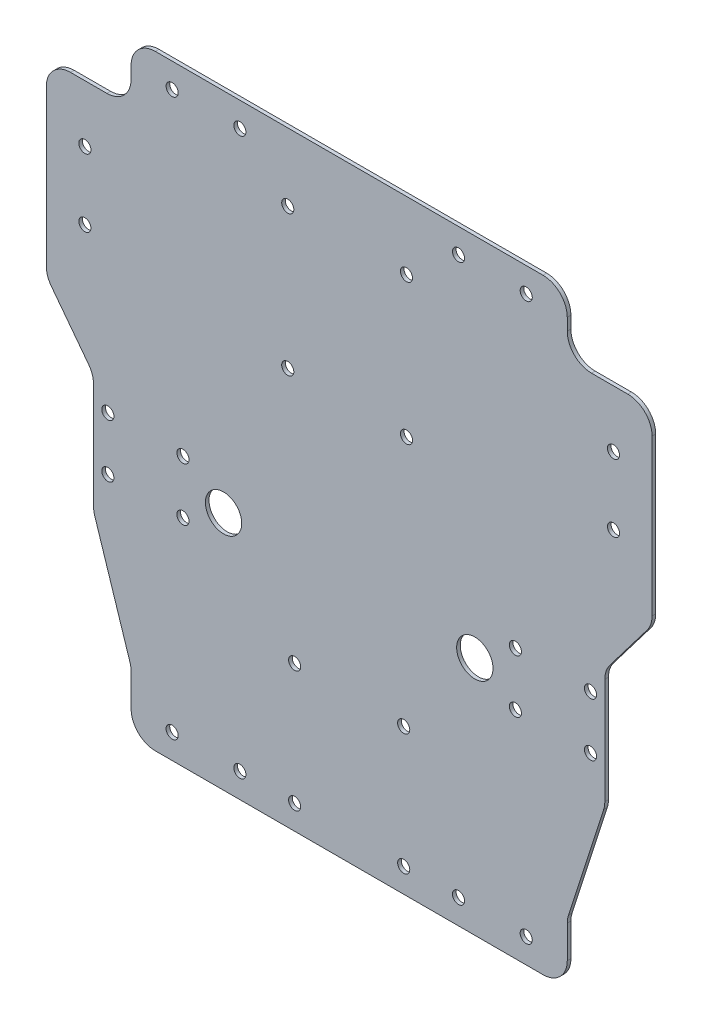
SolidWorks part; units mm, degrees
other "Markup1"
sketch "Sketch7" plane through (25, 0, 0) normal (-0.133, -0.1918, 0.9724) x (0.9904, 0.0125, 0.1379)
material "6061 Alloy"
ref_plane "Front Plane" through (0, 0, 0) normal (0, 0, 1) x (1, 0, 0)
ref_plane "Top Plane" through (0, 0, 0) normal (0, 1, 0) x (1, 0, 0)
ref_plane "Right Plane" through (0, 0, 0) normal (1, 0, 0) x (0, 0, -1)
sketch "Sketch1" plane through (0, 0, 0) normal (0, 0, 1) x (1, 0, 0)
  line L1 (0, 0) -> (300, 0)
  line L2 (0, 0) -> (0, 250)
  line L3 (0, 250) -> (300, 250)
  line L4 (300, 0) -> (300, 250)
  dimension "D1" = 300
  dimension "D2" = 250
extrude "Boss-Extrude1" add sketch "Sketch1" against normal blind 1.5
sketch "Motor Center Line" plane through (0, 0, -1.5) normal (0, 0, -1) x (-1, 0, 0)
  line L0 (0, 100) -> (-300, 100) construction
  line L3 (-300, 250) -> (0, 250) construction
  dimension "D1" = 150
sketch "Sketch2" plane through (0, 0, 0) normal (0, 0, 1) x (1, 0, 0)
  line L0 (150, 0.825) -> (150, -0.825) construction
  line L1 (0, 0) -> (20, 0)
  line L2 (0, 0) -> (0, 20)
  line L3 (0, 20) -> (20, 20)
  line L4 (20, 0) -> (20, 20)
  line L5 (300, 20) -> (280, 20)
  line L6 (280, 0) -> (280, 20)
  line L7 (300, 0) -> (280, 0)
  line L8 (300, 0) -> (300, 20)
  line L10 (0, 125) -> (300, 125) construction
  line L11 (0, 250) -> (0, 0) construction
  line L12 (300, 0) -> (300, 250) construction
  line L13 (300, 250) -> (300, 230)
  line L14 (300, 250) -> (280, 250)
  line L15 (280, 250) -> (280, 230)
  line L16 (300, 230) -> (280, 230)
  line L17 (0, 230) -> (20, 230)
  line L18 (20, 250) -> (20, 230)
  line L19 (0, 250) -> (20, 250)
  line L20 (0, 250) -> (0, 230)
  dimension "D1" = 20
sketch "Sketch3" plane through (0, 0, 0) normal (0, 0, 1) x (1, 0, 0)
  line L0 (150, 250) -> (150, 0) construction
  line L1 (0, 0) -> (25, 0)
  line L2 (0, 0) -> (0, 25)
  line L3 (0, 25) -> (25, 25)
  line L4 (25, 0) -> (25, 25)
  line L5 (300, 250) -> (0, 250) construction
  line L6 (0, 0) -> (300, 0) construction
  line L7 (0, 125) -> (300, 125) construction
  line L8 (0, 250) -> (0, 0) construction
  line L9 (300, 0) -> (300, 250) construction
  line L10 (300, 25) -> (275, 25)
  line L11 (275, 0) -> (275, 25)
  line L12 (300, 0) -> (275, 0)
  line L13 (300, 0) -> (300, 25)
  line L14 (300, 250) -> (300, 225)
  line L15 (300, 250) -> (275, 250)
  line L16 (275, 250) -> (275, 225)
  line L17 (300, 225) -> (275, 225)
  line L18 (0, 225) -> (25, 225)
  line L19 (25, 250) -> (25, 225)
  line L20 (0, 250) -> (25, 250)
  line L21 (0, 250) -> (0, 225)
  line L22 (255.5, 73) -> (275, 47.3437)
  line L23 (255.5, 73) -> (255.5, 121.6874)
  line L24 (255.5, 121.6874) -> (275, 147.3437)
  line L25 (275, 147.3437) -> (300, 147.3437)
  line L26 (300, 147.3437) -> (300, 25)
  line L27 (275, 47.3437) -> (275, 25)
  line L28 (44.5, 73) -> (25, 47.3437)
  line L29 (25, 47.3437) -> (25, 25)
  line L30 (44.5, 73) -> (44.5, 121.6874)
  line L31 (265.5, 121.25) -> (265.5, 78.75) construction
  line L32 (44.5, 121.6874) -> (25, 147.3437)
  line L37 (287.5, 147.3437) -> (287.5, 225)
  line L38 (25, 147.3437) -> (0, 147.3437)
  line L39 (12.5, 147.3437) -> (12.5, 225)
  circle A0 centre (201.85, 99.1258) radius 7.5
  circle A1 centre (98.15, 99.1258) radius 7.5
  ellipse E4 centre (201.85, 99.7743) end of major axis (201.2, 99.7743) minor radius 0.6484 construction
  line M15 (0, 250) -> (0, 0)
  line M16 (0, 0) -> (300, 0)
  line M17 (300, 0) -> (300, 250)
  line M18 (300, 250) -> (0, 250)
  dimension "D3" = 15
  dimension "D1" = 25
  dimension "D2" = 10
  dimension "D4" = 100
extrude "Cut-Extrude1" cut sketch "Sketch3" against normal through all both and the other way through all contours L11 L10 M16 M17 | L25 L24 L23 L10 M17 | L17 L16 M17 M18 | L19 L18 M18 M15 | L3 M15 | L4 L3 M16 M15 | A1 | A0 | L18 M15 | L37 L25 L17 M17 region at (12.5, 12.5, 0) region at (19.2941, 89.7643, 0) region at (287.5, 12.5, 0) region at (6.25, 186.1719, 0) region at (280.7059, 89.7643, 0) region at (12.5, 237.5, 0) region at (293.75, 186.1719, 0) region at (287.5, 237.5, 0) region at (201.85, 99.1258, 0) region at (98.15, 99.1258, 0)
sketch "Sketch4" plane through (0, 0, 0) normal (0, 0, 1) x (1, 0, 0)
  arc A0 (174.9953, 164.0221) -> (172.2953, 164.0221) centre (173.6453, 164.0221) ccw construction
  arc A1 (125.9953, 164.0221) -> (123.2953, 164.0221) centre (124.6453, 164.0221) ccw construction
  arc A4 (125.9953, 222.0221) -> (123.2953, 222.0221) centre (124.6453, 222.0221) ccw construction
  arc A5 (174.9953, 222.0221) -> (172.2953, 222.0221) centre (173.6453, 222.0221) ccw construction
  point P0 (40.9169, 201.47)
  point P1 (40.9169, 173.53)
  point P3 (76.94, 239.84)
  point P4 (104.88, 239.84)
  point P5 (195.12, 239.84)
  point P9 (223.06, 239.84)
  point P11 (259.0831, 201.47)
  point P13 (259.0831, 173.53)
  point P15 (195.12, 10.16)
  point P17 (223.06, 10.16)
  point P19 (76.94, 10.16)
  point P21 (104.88, 10.16)
  point P23 (127.5, 10)
  point P25 (172.5, 10)
  point P27 (127.5, 60)
  point P29 (172.5, 60)
  point P31 (124.6453, 164.0221)
  point P33 (173.6453, 164.0221)
  point P34 (0, 0)
  point P35 (124.6453, 222.0221)
  point P37 (173.6453, 222.0221)
  point P39 (218.6, 111)
  point P41 (249.6, 111)
  point P43 (249.6, 89)
  point P45 (218.6, 89)
  point P47 (81.4, 89.0063)
  point P49 (50.4, 89.0063)
  point P51 (81.4, 111.0063)
  point P53 (50.4, 111.0063)
  point P55 (0, 0)
  point P57 (0, 0)
  point P61 (0, 0)
  point P62 (0, 0)
  point P66 (0, 0)
  point P68 (0, 0)
  point P69 (0, 0)
  point P71 (0, 0)
sketch "Sketch6" plane through (0, 0, 0) normal (0, 0, 1) x (1, 0, 0)
  line L1 (275, 0) -> (240, 0)
  line L2 (275, 0) -> (275, 25)
  line L3 (275, 25) -> (240, 25)
  line L4 (240, 0) -> (240, 25)
  line L5 (240, 25) -> (255.5, 73)
  line L6 (150, 250) -> (150, 0) construction
  line L7 (275, 250) -> (25, 250) construction
  line L8 (25, 0) -> (275, 0) construction
  line L9 (60, 25) -> (44.5, 73)
  line L10 (25, 25) -> (60, 25)
  line L11 (60, 0) -> (60, 25)
  line L12 (25, 0) -> (60, 0)
  line L13 (25, 0) -> (25, 25)
  line L14 (275, 250) -> (240, 250)
  line L15 (25, 225) -> (60, 225)
  line L16 (25, 225) -> (25, 250)
  line L17 (25, 250) -> (60, 250)
  line L18 (60, 225) -> (60, 250)
  line L19 (240, 225) -> (240, 250)
  line L20 (275, 225) -> (240, 225)
  line L21 (275, 225) -> (275, 250)
  line L22 (25, 225) -> (25, 147.3437)
  line L23 (275, 147.3437) -> (275, 225)
  line L24 (287.5, 225) -> (287.5, 147.3437)
  line L25 (287.5, 147.3437) -> (275, 147.3437)
  line L26 (25, 225) -> (12.5, 225)
  line L27 (12.5, 225) -> (12.5, 147.3437)
  line L28 (12.5, 147.3437) -> (25, 147.3437)
  line M11 (275, 0) -> (275, 47.3437)
  line M12 (275, 47.3437) -> (255.5, 73)
  line M15 (275, 147.3437) -> (287.5, 147.3437)
  line M16 (287.5, 147.3437) -> (287.5, 225)
  line M17 (287.5, 225) -> (275, 225)
  line M18 (275, 225) -> (275, 250)
  line M19 (275, 250) -> (25, 250)
  line M20 (25, 250) -> (25, 225)
  line M21 (25, 225) -> (12.5, 225)
  line M22 (12.5, 225) -> (12.5, 147.3437)
  line M23 (12.5, 147.3437) -> (25, 147.3437)
  line M26 (44.5, 73) -> (25, 47.3437)
  line M27 (25, 47.3437) -> (25, 0)
  line M28 (25, 0) -> (275, 0)
  dimension "D1" = 25
  dimension "D2" = 35
extrude "Cut-Extrude3" cut sketch "Sketch6" against normal through all contours L11 L10 M28 M27 | L10 L9 M27 M26 | L4 L3 M28 M11 | L5 L3 M11 M12 | L15 L18 M19 M20 | L20 L19 M18 M19 | L22 M21 M22 M23 | L23 M15 M16 M17 region at (42.5, 12.5, 0) region at (257.5, 12.5, 0) region at (259.2359, 42.5338, 0) region at (40.7641, 42.5338, 0) region at (257.5, 237.5, 0) region at (281.25, 186.1719, 0) region at (18.75, 186.1719, 0) region at (42.5, 237.5, 0)
sketch "Sketch5" plane through (0, 0, 0) normal (0, 0, 1) x (1, 0, 0)
  circle A0 centre (76.94, 10.16) radius 2.5
  dimension "D1" = 5
extrude "Cut-Extrude2" cut sketch "Sketch5" against normal through all both
pattern_sketch "Sketch-Pattern1" of "Cut-Extrude2" driven by "Sketch4"
fillet "Fillet1" radius 10 16 edges at (255.5, 121.6874, -0.75) (44.5, 121.6874, -0.75) (240, 250, -0.75) (240, 225, -0.75) (60, 250, -0.75) (60, 225, -0.75) (44.5, 73, -0.75) (60, 25, -0.75) (60, 0, -0.75) (255.5, 73, -0.75) (240, 25, -0.75) (240, 0, -0.75) (275, 225, -0.75) (275, 147.3437, -0.75) (25, 225, -0.75) (25, 147.3437, -0.75)
